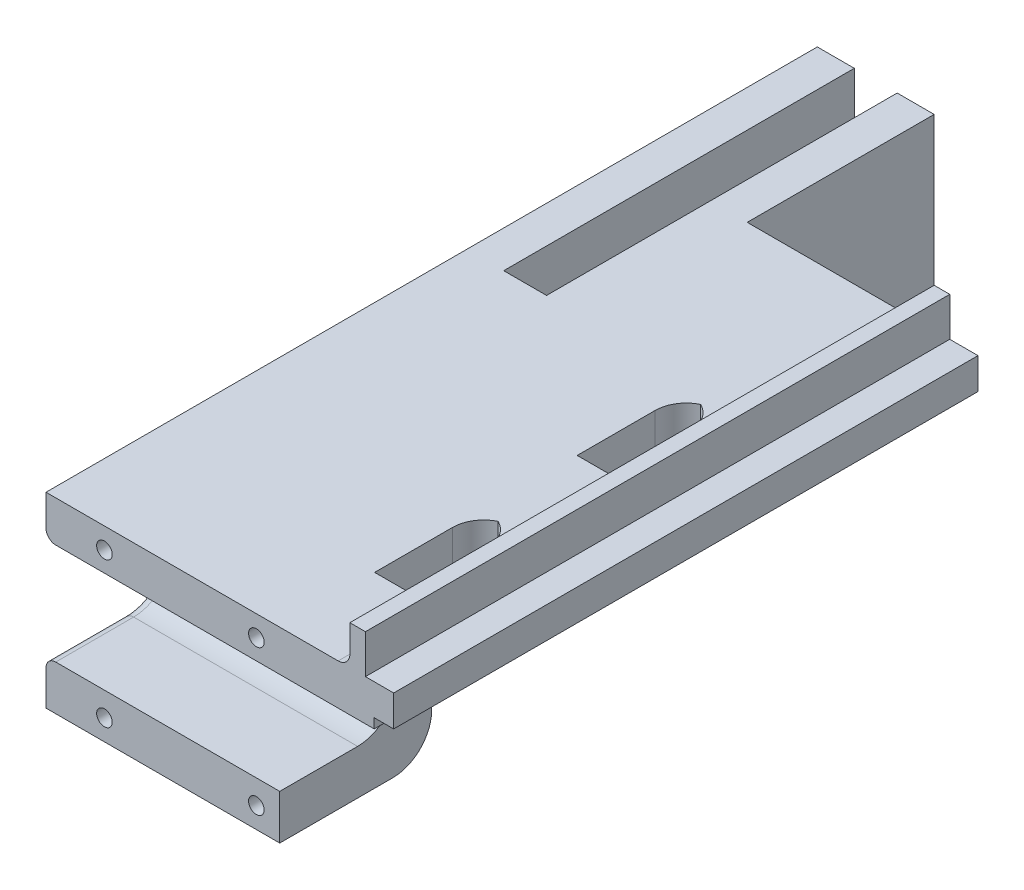
SolidWorks part; units mm, degrees
ref_plane "Alzado" through (0, 0, 0) normal (0, 0, 1) x (1, 0, 0)
ref_plane "Planta" through (0, 0, 0) normal (0, 1, 0) x (1, 0, 0)
ref_plane "Vista lateral" through (0, 0, 0) normal (1, 0, 0) x (0, 0, -1)
sketch "Croquis1" plane through (0, 0, 0) normal (0, 0, 1) x (1, 0, 0)
  line L1 (-66.2162, 31.0113) -> (-6.2162, 31.0113)
  line L2 (-66.2162, 31.0113) -> (-66.2162, -16.9887)
  line L3 (-66.2162, -16.9887) -> (-6.2162, -16.9887)
  line L4 (-6.2162, 31.0113) -> (-6.2162, -16.9887)
  dimension "D1" = 48
  dimension "D2" = 60
extrude "Saliente-Extruir1" add sketch "Croquis1" along normal blind 6
sketch "Croquis4" plane through (0, 0, 6) normal (0, 0, 1) x (1, 0, 0)
  line L0 (-66.2162, 31.0113) -> (-66.2162, 19.5113)
  line L1 (-66.2162, 31.0113) -> (-66.2162, -16.9887) construction
  line L3 (-66.2162, -5.4887) -> (-66.2162, -16.9887)
  line L4 (-66.2162, 31.0113) -> (-6.2162, 31.0113)
  line L6 (-6.2162, 31.0113) -> (-6.2162, 19.5113)
  line L7 (-6.2162, -16.9887) -> (-6.2162, 31.0113) construction
  line L8 (-6.2162, 19.5113) -> (-66.2162, 19.5113)
  line L9 (-66.2162, -5.4887) -> (-6.2162, -5.4887)
  line L10 (-6.2162, -5.4887) -> (-6.2162, -16.9887)
  line L11 (-6.2162, -16.9887) -> (-66.2162, -16.9887)
  dimension "D1" = 25
extrude "Saliente-Extruir3" add sketch "Croquis4" along normal blind 30
sketch "Croquis3" plane through (0, 0, 6) normal (0, 0, 1) x (1, 0, 0)
  circle A0 centre (-51.2162, 25.6613) radius 2.125
  circle A1 centre (-12.2162, 25.6613) radius 2.125
  circle A2 centre (-12.2162, -11.6387) radius 2.125
  circle A3 centre (-51.2162, -11.6387) radius 2.125
  dimension "D7" = 4.25
  dimension "D9" = 4.25
  dimension "D10" = 4.25
  dimension "D2" = 4.25
  dimension "D3" = 37.3
  dimension "D4" = 39
sketch "Croquis5" plane through (0, 0, 36) normal (0, 0, 1) x (1, 0, 0)
  circle A0 centre (-51.2162, 25.6613) radius 2
  circle A1 centre (-12.2162, 25.6613) radius 2
  circle A2 centre (-12.2162, -11.6387) radius 2
  circle A3 centre (-51.2162, -11.6387) radius 2
  dimension "D1" = 4
  dimension "D2" = 4
  dimension "D3" = 4
  dimension "D4" = 4
extrude "Cortar-Extruir3" cut sketch "Croquis5" against normal blind 16
sketch "Croquis6" plane through (0, 0, 0) normal (0, 0, -1) x (-1, 0, 0)
  line L0 (66.2162, -16.9887) -> (6.2162, -16.9887) construction
  line L1 (66.2162, 31.0113) -> (36.2162, 31.0113)
  line L2 (66.2162, 31.0113) -> (66.2162, -16.9887)
  line L3 (66.2162, -16.9887) -> (36.2162, -16.9887)
  line L4 (36.2162, 31.0113) -> (36.2162, -16.9887)
  dimension "D1" = 30
extrude "Saliente-Extruir4" add sketch "Croquis6" along normal blind 162
sketch "Croquis7" plane through (0, 0, -162) normal (0, 0, -1) x (-1, 0, 0)
  circle A0 centre (51.2162, 7.0113) radius 2
  dimension "D1" = 4
extrude "Cortar-Extruir4" cut sketch "Croquis7" against normal blind 16
sketch "Croquis8" plane through (0, 0, -162) normal (0, 0, -1) x (-1, 0, 0)
  line L0 (41.2162, 12.0113) -> (41.2162, 9.5131)
  line L10 (36.2162, 12.0113) -> (41.2162, 12.0113)
  line L11 (36.2162, 12.0113) -> (36.2162, 2.0113)
  line L12 (36.2162, 2.0113) -> (41.2162, 2.0113)
  line L21 (41.2162, 9.5131) -> (44.2162, 9.5131)
  line L23 (41.2162, 4.5131) -> (44.2162, 4.5131)
  line L24 (44.2162, 9.5131) -> (44.2162, 4.5131)
  line L25 (41.2162, 2.0113) -> (41.2162, 4.5131)
  dimension "D1" = 5
  dimension "D2" = 3
  dimension "D3" = 5
sketch "Croquis11" plane through (-36.2162, 0, 0) normal (1, 0, 0) x (0, 0, -1)
  line L1 (-36, 19.5113) -> (-36, 31.0113) construction
  line L4 (-36, 19.5113) -> (-36, 31.0113)
  line L6 (-36, 19.5113) -> (114, 19.5113)
  line L7 (114, 19.5113) -> (114, 31.0113)
  line L8 (162, 31.0113) -> (0, 31.0113) construction
  line L9 (162, 31.0113) -> (0, 31.0113) construction
  line L10 (-36, 31.0113) -> (114, 31.0113)
  dimension "D1" = 150
extrude "Saliente-Extruir6" add sketch "Croquis11" along normal blind 59.25
sketch "Croquis12" plane through (0, 31.0113, 0) normal (0, 1, 0) x (1, 0, 0)
  line L0 (23.0338, -36) -> (-66.2162, -36) construction
  line L1 (15.7838, -36) -> (11.7838, -36)
  line L2 (-66.2162, -36) -> (-66.2162, 162) construction
  line L3 (-66.2162, -36) -> (-66.2162, 162) construction
  line L4 (15.7838, -36) -> (15.7838, 114)
  line L5 (15.7838, 114) -> (11.7838, 114)
  line L6 (23.0338, 114) -> (-36.2162, 114) construction
  line L7 (11.7838, 114) -> (11.7838, -36)
  dimension "D1" = 82
  dimension "D2" = 150
  dimension "D3" = 4
extrude "Saliente-Extruir7" add sketch "Croquis12" along normal blind 10
sketch "Croquis14" plane through (0, 0, -114) normal (0, 0, -1) x (-1, 0, 0)
  line L0 (-23.0338, 23.0113) -> (-18.0338, 23.0113)
  line L1 (-18.0338, 23.0113) -> (-18.0338, 19.5113)
  line L2 (-23.0338, 23.0113) -> (-23.0338, 19.5113)
  line L3 (-23.0338, 19.5113) -> (-18.0338, 19.5113)
  line L4 (36.2162, 19.5113) -> (36.2162, 31.0113)
  line L5 (36.2162, 31.0113) -> (-11.7838, 31.0113)
  line L6 (-23.0338, 31.0113) -> (-23.0338, 19.5113)
  line L7 (-23.0338, 19.5113) -> (36.2162, 19.5113)
  line L8 (36.2162, 19.5113) -> (36.2162, 31.0113) construction
  line L9 (36.2162, 31.0113) -> (-11.7838, 31.0113) construction
  line L10 (-23.0338, 31.0113) -> (-23.0338, 19.5113) construction
  line L11 (-23.0338, 19.5113) -> (36.2162, 19.5113) construction
  line L20 (-11.7838, 31.0113) -> (-11.7838, 41.0113)
  line L22 (-11.7838, 41.0113) -> (-15.7838, 41.0113)
  line L24 (-15.7838, 41.0113) -> (-15.7838, 31.0113)
  line L26 (-15.7838, 31.0113) -> (-23.0338, 31.0113)
  line L27 (-15.7838, 31.0113) -> (-23.0338, 31.0113) construction
  dimension "D2" = 5
  dimension "D3" = 8
  dimension "D1" = 0
extrude "Cortar-Extruir6" cut sketch "Croquis14" against normal through all both and the other way through all
sketch "Croquis15" plane through (0, 0, -162) normal (0, 0, -1) x (-1, 0, 0)
  line L0 (51.2162, 45.0729) -> (51.2162, 16.9496) construction
  line L1 (56.7162, 20.0113) -> (45.7162, 20.0113)
  line L2 (45.7162, 20.0113) -> (45.7162, 31.0113)
  line L3 (56.7162, 20.0113) -> (56.7162, 31.0113)
  line L4 (66.2162, -16.9887) -> (66.2162, 31.0113)
  line L5 (66.2162, 31.0113) -> (36.2162, 31.0113)
  line L6 (36.2162, 31.0113) -> (36.2162, -16.9887)
  line L7 (36.2162, -16.9887) -> (66.2162, -16.9887)
  line L8 (66.2162, -16.9887) -> (66.2162, 31.0113) construction
  line L9 (66.2162, 31.0113) -> (36.2162, 31.0113) construction
  line L10 (56.7162, 31.0113) -> (45.7162, 31.0113)
  point P6 (51.2162, 31.0113)
  point P10 (51.2162, 20.0113)
  dimension "D2" = 11
  dimension "D3" = 11
  dimension "D1" = 0
extrude "Cortar-Extruir7" cut sketch "Croquis15" against normal blind 90 and the other way through all
sketch "Croquis16" plane through (-66.2162, 0, 0) normal (-1, 0, 0) x (0, 0, 1)
  line L0 (6, 19.5113) -> (6, 20.5113)
  line L1 (6, 20.5113) -> (36, 20.5113)
  line L2 (36, 31.0113) -> (36, 19.5113) construction
  line L3 (6, 19.5113) -> (36, 19.5113)
  line L4 (36, 19.5113) -> (36, 20.5113)
  dimension "D1" = 1
extrude "Cortar-Extruir10" cut sketch "Croquis16" against normal through all contours L1 L4 L3 L0
fillet "Redondeo1" radius 10 2 edges at (-36.2162, -5.4887, 6) (-24.0912, 20.5113, 6)
sketch "Croquis20" plane through (0, 0, 0) normal (0, 0, -1) x (-1, 0, 0)
  line L1 (6.2162, 19.5113) -> (36.2162, 19.5113)
  line L2 (6.2162, 19.5113) -> (6.2162, -16.9887)
  line L3 (6.2162, -16.9887) -> (36.2162, -16.9887)
  line L4 (36.2162, 19.5113) -> (36.2162, -16.9887)
extrude "Saliente-Extruir8" add sketch "Croquis20" along normal blind 50
sketch "Croquis21" plane through (0, 19.5113, 0) normal (0, -1, 0) x (1, 0, 0)
  line L1 (2.7838, 11.6411) -> (-6.2162, 11.6411)
  line L2 (2.7838, 11.6411) -> (2.7838, -16.3589)
  line L3 (2.7838, -16.3589) -> (-6.2162, -16.3589)
  line L4 (-6.2162, 11.6411) -> (-6.2162, -16.3589)
  line L5 (18.0338, 11.6411) -> (-6.2162, 11.6411) construction
  line L6 (-6.2162, 36) -> (-6.2162, -50) construction
  line L12 (-1.7162, 20.4456) -> (-1.7162, -78.1671) construction
  line L13 (2.7838, -40.3589) -> (2.7838, -68.3589)
  line L14 (2.7838, -40.3589) -> (-6.2162, -40.3589)
  line L15 (-6.2162, -40.3589) -> (-6.2162, -68.3589)
  line L16 (2.7838, -68.3589) -> (-6.2162, -68.3589)
  point P10 (-1.7162, -16.3589)
  dimension "D1" = 9
  dimension "D2" = 28
  dimension "D3" = 2
  dimension "D4" = 24
extrude "Cortar-Extruir11" cut sketch "Croquis21" against normal blind 40
sketch "Croquis22" plane through (0, 0, -50) normal (0, 0, -1) x (-1, 0, 0)
  line L1 (36.2162, 19.5113) -> (6.2162, 19.5113)
  line L2 (36.2162, 19.5113) -> (36.2162, -16.9887)
  line L3 (36.2162, -16.9887) -> (6.2162, -16.9887)
  line L4 (6.2162, 19.5113) -> (6.2162, -16.9887)
extrude "Cortar-Extruir13" cut sketch "Croquis22" against normal blind 47
fillet "Redondeo3" radius 10 1 edges at (-21.2162, -16.9887, -3)
sketch "Croquis23" plane through (0, 0, 36) normal (0, 0, 1) x (1, 0, 0)
  circle A0 centre (-12.2162, -11.6387) radius 2 construction
  circle A1 centre (-51.2162, -11.6387) radius 2 construction
  circle A2 centre (-12.2162, 25.6613) radius 2 construction
  circle A3 centre (-51.2162, 25.6613) radius 2 construction
  circle A4 centre (-12.2162, -11.6387) radius 2
  circle A5 centre (-51.2162, -11.6387) radius 2
  circle A6 centre (-12.2162, 25.6613) radius 2
  circle A7 centre (-51.2162, 25.6613) radius 2
extrude "Cortar-Extruir14" cut sketch "Croquis23" against normal blind 16
fillet "Redondeo4" radius 3 1 edges at (11.7838, 31.0113, -39)
sketch "Croquis24" plane through (0, 0, -162) normal (0, 0, -1) x (-1, 0, 0)
  line L0 (36.2162, -16.9887) -> (66.2162, -16.9887) construction
  line L1 (36.2162, -16.9887) -> (66.2162, -16.9887) construction
  line L2 (51.2162, 1.6971) -> (51.2162, -35.6746) construction
  line L3 (48.6162, -16.9887) -> (48.6162, -12.9887)
  line L4 (48.6162, -12.9887) -> (44.2162, -12.9887)
  line L5 (44.2162, -12.9887) -> (44.2162, -8.9887)
  line L6 (44.2162, -8.9887) -> (58.2162, -8.9887)
  line L7 (48.6162, -16.9887) -> (53.8162, -16.9887)
  line L8 (58.2162, -12.9887) -> (58.2162, -8.9887)
  line L9 (53.8162, -12.9887) -> (58.2162, -12.9887)
  line L10 (53.8162, -16.9887) -> (53.8162, -12.9887)
  point P5 (51.2162, -16.9887)
  point P12 (51.2162, -16.9887)
  point P13 (51.2162, -8.9887)
  dimension "D1" = 4
  dimension "D2" = 4
  dimension "D3" = 7
  dimension "D4" = 2.6
extrude "Cortar-Extruir15" cut sketch "Croquis24" against normal blind 170
fillet "Redondeo5" radius 6 1 edges at (-36.2162, 19.5113, -58.5)
fillet "Redondeo6" radius 2.5 5 edges at (-66.2162, 20.5113, 26) (-66.2162, 17.5823, 8.9289) (-66.2162, 7.5113, 6) (-66.2162, -2.5598, 8.9289) (-66.2162, -5.4887, 26)
fillet "Redondeo7" radius 8 4 edges at (2.7838, 25.2613, -68.3589) (-6.2162, 25.2613, -68.3589) (-6.2162, 25.2613, -16.3589) (2.7838, 25.2613, -16.3589)
